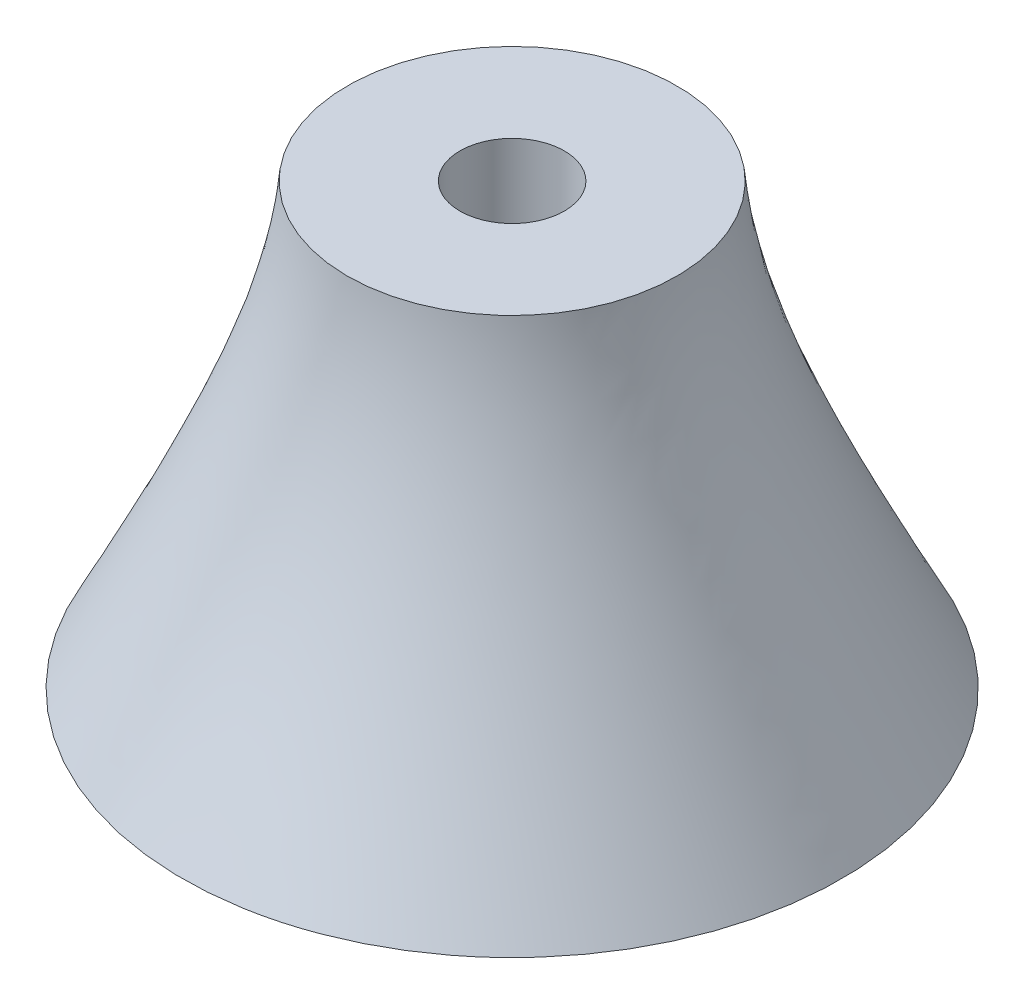
SolidWorks part; units mm, degrees
ref_plane "Ön Düzlem" through (0, 0, 0) normal (0, 0, 1) x (1, 0, 0)
ref_plane "Üst Düzlem" through (0, 0, 0) normal (0, 1, 0) x (1, 0, 0)
ref_plane "Sağ Düzlem" through (0, 0, 0) normal (1, 0, 0) x (0, 0, -1)
sketch "Çizim1" plane through (0, 0, 0) normal (0, 1, 0) x (1, 0, 0)
  circle A0 centre (0, 0) radius 30
  dimension "D1" = 60
ref_plane "Düzlem1" through (0, 20, 0) normal (0, 1, 0) x (1, 0, 0)
sketch "Çizim2" plane through (0, 20, 0) normal (0, 1, 0) x (1, 0, 0)
  circle A0 centre (0, 0) radius 15
  dimension "D1" = 30
ref_plane "Düzlem2" through (0, 40, 0) normal (0, 1, 0) x (1, 0, 0)
sketch "Çizim3" plane through (0, 40, 0) normal (0, 1, 0) x (1, 0, 0)
  circle A0 centre (0, 0) radius 15
  dimension "D1" = 30
loft "Loft1" add profiles "Çizim3", "Çizim1" connector at (-14.8064, 40, -2.4024) connector at (-14.601, 0, -26.2071)
sketch "Çizim4" plane through (0, 40, 0) normal (0, 1, 0) x (1, 0, 0)
  circle A0 centre (0, 0) radius 4.75
  dimension "D1" = 9.5
extrude "Kes-Ekstrüzyon1" cut sketch "Çizim4" against normal blind 60
